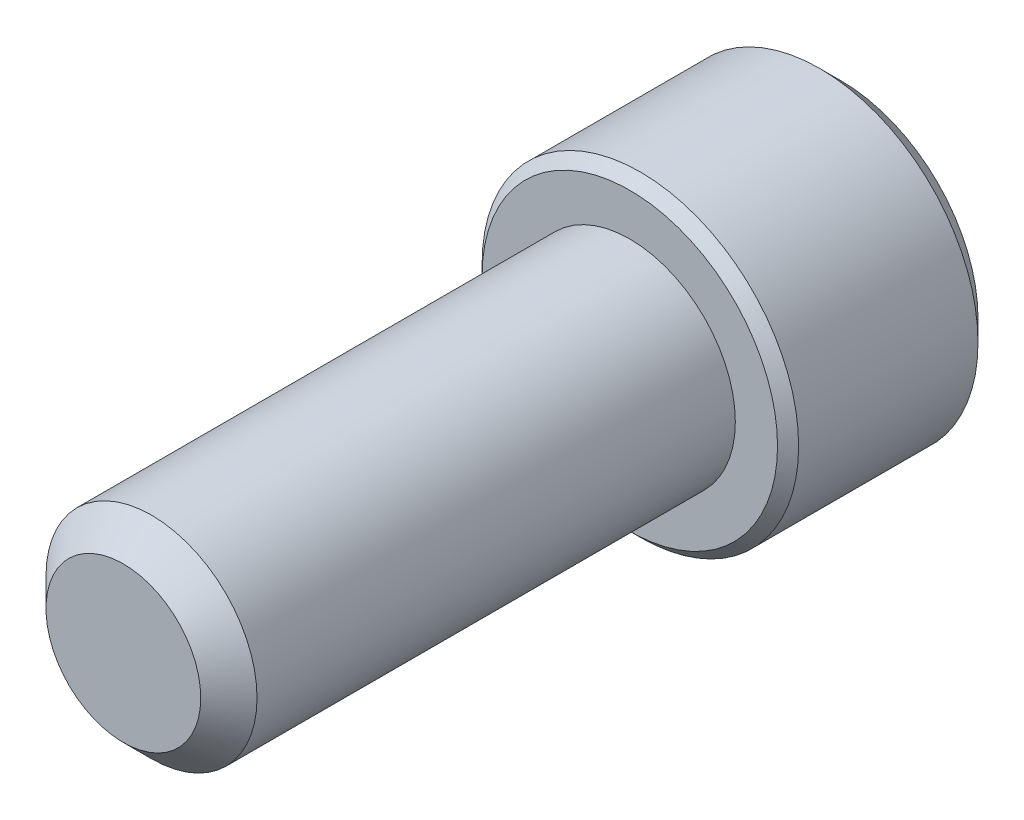
SolidWorks part; units mm, degrees
material "Alloy Steel"
ref_plane "Front Plane" through (0, 0, 0) normal (0, 0, 1) x (1, 0, 0)
ref_plane "Top Plane" through (0, 0, 0) normal (0, 1, 0) x (1, 0, 0)
ref_plane "Right Plane" through (0, 0, 0) normal (1, 0, 0) x (0, 0, -1)
sketch "Sketch1" plane through (0, 0, 0) normal (0, 0, 1) x (1, 0, 0)
  line L0 (0, 3.9688) -> (0, -3.9688) construction
  circle A0 centre (0, 0) radius 3.9688
  dimension "OD" = 7.9375
extrude "Extrude1" add sketch "Sketch1" against normal blind 19.05
sketch "Sketch2" plane through (0, 0, 0) normal (0, 0, 1) x (1, 0, 0)
  circle A0 centre (0, 0) radius 3.9688 construction
  circle A1 centre (0, 0) radius 3.9688
curve "Helix/Spiral1" pitch 1.4111 height 20.4611 turns 14.5 parameters "pitch"=1.4111
chamfer "Chamfer3" distance 1.0583 angle 45 1 edges at (3.9688, 0, 0)
sketch "Sketch3" plane through (0, 0, 0) normal (1, 0, 0) x (0, 0, -1)
  line L0 (-1.2347, 3.9688) -> (-0.7056, 3.0522)
  line L1 (-0.7056, 3.0522) -> (-0.5292, 3.0522)
  line L2 (-0.5292, 3.0522) -> (0, 3.9688)
  line L3 (-1.2347, 3.9688) -> (0, 3.9688)
  line L4 (-0.6174, 3.9688) -> (-0.6174, 3.0522) construction
  line L5 (-0.9701, 3.5105) -> (-0.2646, 3.5105) construction
  line L6 (0, 3.9688) -> (0, -3.9688) construction
  dimension "D1" = 0.1764
  dimension "D2" = 0.7056
  dimension "D3" = 60
sweep "Cut-Sweep1" [suppressed] cut profiles "Sketch3" path "Helix/Spiral1"
sketch "Sketch6" plane through (0, 0, -19.05) normal (0, 0, -1) x (-1, 0, 0)
  circle A0 centre (0, 0) radius 5.9531
  dimension "head dia" = 11.9062
extrude "Extrude2" add sketch "Sketch6" along normal blind 7.9375
sketch "Sketch7" plane through (0, 0, -26.9875) normal (0, 0, -1) x (-1, 0, 0)
  line L1 (0, 3.6662) -> (-3.175, 1.8331)
  line L2 (-3.175, 1.8331) -> (-3.175, -1.8331)
  line L3 (-3.175, -1.8331) -> (0, -3.6662)
  line L4 (0, -3.6662) -> (3.175, -1.8331)
  line L5 (3.175, -1.8331) -> (3.175, 1.8331)
  line L6 (3.175, 1.8331) -> (0, 3.6662)
  circle A0 centre (0, 0) radius 3.175 construction
  dimension "hex dia" = 6.35
extrude "Cut-Extrude1" cut sketch "Sketch7" against normal blind 4.7625
sketch "Sketch8" plane through (0, 0, -26.9875) normal (0, 0, -1) x (-1, 0, 0)
  circle A0 centre (0, 0) radius 3.6662
extrude "Cut-Extrude2" cut sketch "Sketch8" against normal blind 0.7937 draft 45
chamfer "Chamfer1" distance 0.7937 angle 45 1 edges at (-5.9531, 0, -26.9875)
chamfer "Chamfer2" distance 0.3969 angle 45 1 edges at (-5.9531, 0, -19.05)
sketch "Sketch9" plane through (0, 0, 0) normal (1, 0, 0) x (0, 0, -1)
  line L0 (0, 3.9688) -> (0, -3.9688) construction
  line L1 (7.7611, 3.9688) -> (7.7611, -3.9688) construction
  line L2 (19.05, 5.9531) -> (19.05, -5.9531) construction
  line L3 (26.9875, 5.9531) -> (26.9875, -5.9531) construction
  line L4 (26.9875, 0) -> (0, 0) construction
  dimension "D1" = 7.7611
  dimension "D2" = 7.9375
  dimension "D3" = 11.9062
  dimension "D4" = 19.05
move or copy body "Body-Move/Copy1" [suppressed] bodies to move or copy 107
equation "\"D3@Helix/Spiral1\" = \"screw length@Extrude1\"+\"pitch@Helix/Spiral1\""
equation "\"D1@Sketch3\" = \"pitch@Helix/Spiral1\"*.125"
equation "\"D2@Sketch3\" = \"pitch@Helix/Spiral1\"*.5"
equation "\"D1@Cut-Extrude1\" = \"hex dia@Sketch7\"*.75"
equation "\"D1@Chamfer1\" = \"head depth@Extrude2\"/10"
equation "\"D1@Sketch9\" = \"pitch@Helix/Spiral1\"*5.5"
equation "\"D1@Chamfer2\" = \"D1@Chamfer1\"/2"
equation "\"D1@Cut-Extrude2\" = \"D1@Chamfer2\"*2"
equation "\"D1@Chamfer3\" = \"pitch@Helix/Spiral1\"*.750"
equation "\"D2@Sketch9\" = \"head depth@Extrude2\""
equation "\"D3@Sketch9\" = \"head dia@Sketch6\""
equation "\"D4@Sketch9\" = \"screw length@Extrude1\""
